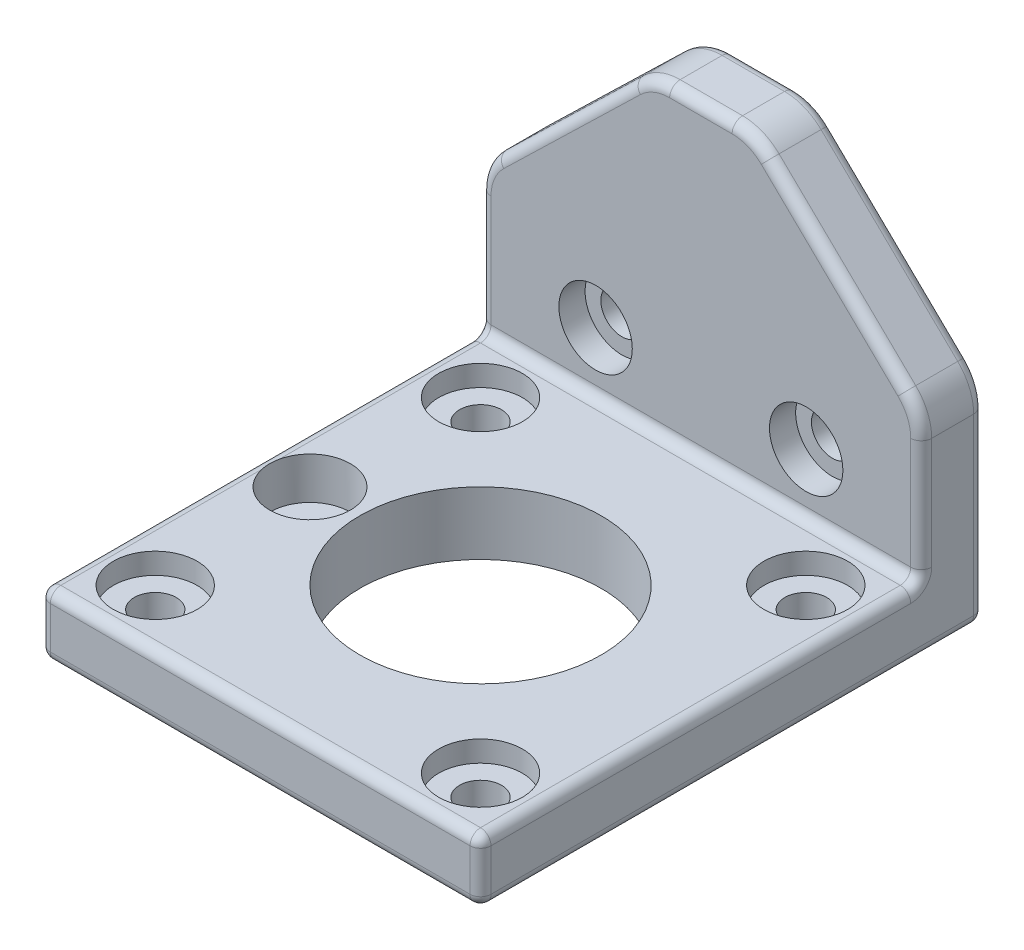
SolidWorks part; units mm, degrees
ref_plane "Front Plane" through (0, 0, 0) normal (0, 0, 1) x (1, 0, 0)
ref_plane "Top Plane" through (0, 0, 0) normal (0, 1, 0) x (1, 0, 0)
ref_plane "Right Plane" through (0, 0, 0) normal (1, 0, 0) x (0, 0, -1)
sketch "Sketch1" plane through (0, 0, 0) normal (0, 1, 0) x (1, 0, 0)
  line L1 (-21, 21) -> (21, 21)
  line L2 (-21, 21) -> (-21, -21)
  line L3 (-21, -21) -> (21, -21)
  line L4 (21, 21) -> (21, -21)
  line L5 (-21, 21) -> (21, -21) construction
  line L6 (-21, -21) -> (21, 21) construction
  point P0 (0, 0)
  dimension "D1" = 42
  dimension "D2" = 42
extrude "Boss-Extrude1" add sketch "Sketch1" along normal blind 6
sketch "Sketch3" plane through (0, 6, 0) normal (0, 1, 0) x (1, 0, 0)
  line L0 (0, -15.5) -> (0, 15.5) construction
  line L1 (-15.5, 0) -> (15.5, 0) construction
  line L2 (-15.5, 15.5) -> (15.5, 15.5) construction
  line L3 (15.5, 15.5) -> (15.5, -15.5) construction
  line L4 (15.5, -15.5) -> (-15.5, -15.5) construction
  line L5 (-15.5, -15.5) -> (-15.5, 15.5) construction
  circle A0 centre (-15.5, 15.5) radius 3.9905
  circle A1 centre (15.5, 15.5) radius 3.9905
  circle A2 centre (-15.5, -15.5) radius 3.9905
  circle A3 centre (15.5, -15.5) radius 3.9905
  point P12 (0, 0)
  point P16 (0, 0)
  point P17 (0, 15.5)
  point P20 (15.5, 0)
  dimension "D1" = 7.981
  dimension "D2" = 31
  dimension "D3" = 31
extrude "Cut-Extrude1" cut sketch "Sketch3" against normal blind 2
sketch "Sketch4" plane through (0, 6, 0) normal (0, 1, 0) x (1, 0, 0)
  circle A0 centre (0, 0) radius 11.5
  circle A1 centre (15.5, 15.5) radius 2
  circle A2 centre (-15.5, 15.5) radius 2
  circle A3 centre (-15.5, -15.5) radius 2
  circle A4 centre (15.5, -15.5) radius 2
  dimension "D1" = 4
  dimension "D2" = 23
extrude "Cut-Extrude2" cut sketch "Sketch4" against normal through all
sketch "Sketch5" plane through (0, 0, -21) normal (0, 0, -1) x (-1, 0, 0)
  line L0 (0, 9.875) -> (0, 19.75) construction
  line L2 (-21, 19.75) -> (-21, 0)
  line L3 (-21, 0) -> (21, 0)
  line L4 (21, 19.75) -> (21, 0)
  line L5 (-21, 19.75) -> (21, 0) construction
  line L6 (-21, 0) -> (21, 19.75) construction
  line L7 (-5, 35.25) -> (5, 35.25)
  line L13 (5, 35.25) -> (21, 19.75)
  line L14 (-5, 35.25) -> (-21, 19.75)
  point P0 (0, 9.875)
  point P6 (0, 27.5)
  dimension "D1" = 35.25
  dimension "D2" = 19.75
  dimension "D3" = 16
  dimension "D4" = 16
  dimension "D5" = 15.5
extrude "Boss-Extrude2" add sketch "Sketch5" along normal blind 6
sketch "Sketch6" plane through (0, 0, -21) normal (0, 0, 1) x (1, 0, 0)
  line L0 (-10.035, 11.75) -> (10.035, 11.75) construction
  line L1 (0, 11.75) -> (0, 0) construction
  circle A0 centre (-10.035, 11.75) radius 3.5
  circle A1 centre (10.035, 11.75) radius 3.5
  dimension "D1" = 7
  dimension "D2" = 7
  dimension "D3" = 11.75
  dimension "D4" = 20.07
extrude "Cut-Extrude3" cut sketch "Sketch6" against normal blind 2.5
sketch "Sketch7" plane through (0, 0, -21) normal (0, 0, 1) x (1, 0, 0)
  circle A0 centre (-10.035, 11.75) radius 2
  circle A1 centre (10.035, 11.75) radius 2
  dimension "D1" = 4
extrude "Cut-Extrude4" cut sketch "Sketch7" against normal through all
fillet "Fillet1" radius 5 4 edges at (21, 19.75, -24) (5, 35.25, -24) (-5, 35.25, -24) (-21, 19.75, -24)
sketch "Sketch8" plane through (0, 6, 0) normal (0, 1, 0) x (1, 0, 0)
  line L0 (0, 0) -> (-16.25, 0) construction
  circle A0 centre (-16.25, 0) radius 3.8413
  dimension "D1" = 7.6825
  dimension "D2" = 16.25
extrude "Cut-Extrude5" cut sketch "Sketch8" against normal blind 4
fillet "Fillet2" radius 1 28 edges at (0, 35.25, -21) (4.852, 34.8844, -21) (-4.852, 34.8844, -21) (12.9666, 27.5323, -21) (-12.9666, 27.5323, -21) (20.6041, 19.5823, -21) (-20.6041, 19.5823, -21) (21, 11.8161, -21) (-21, 11.8161, -21) (-21, 8.8161, -27) (-20.6041, 19.5823, -27) (-12.9666, 27.5323, -27) (-4.852, 34.8844, -27) (21, 8.8161, -27) (20.6041, 19.5823, -27) (12.9666, 27.5323, -27) (4.852, 34.8844, -27) (0, 0, -27) (0, 35.25, -27) (0, 6, -21) (0, 0, 21) (0, 6, 21) (21, 0, -3) (21, 6, 0) (-21, 0, -3) (-21, 6, 0) (-21, 3, 21) (21, 3, 21)
